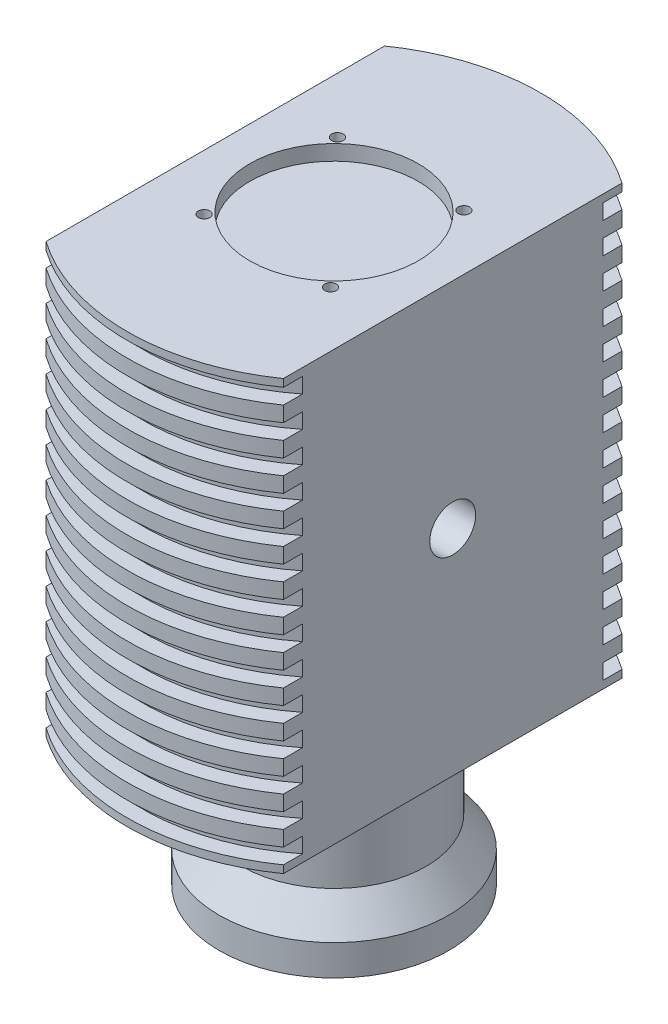
SolidWorks part; units mm, degrees
ref_plane "Front Plane" through (0, 0, 0) normal (0, 0, 1) x (1, 0, 0)
ref_plane "Top Plane" through (0, 0, 0) normal (0, 1, 0) x (1, 0, 0)
ref_plane "Right Plane" through (0, 0, 0) normal (1, 0, 0) x (0, 0, -1)
sketch "Sketch1" plane through (0, 0, 0) normal (0, 0, 1) x (1, 0, 0)
  line L0 (0, 0) -> (30, 0)
  line L1 (30, 0) -> (30, 8)
  line L2 (30, 8) -> (24, 16)
  line L3 (24, 16) -> (24, 40)
  line L9 (0, 76.2123) -> (0, -32.816) construction
  line L17 (24, 40) -> (54, 40)
  line L18 (54, 40) -> (54, 42)
  line L19 (54, 42) -> (50, 42)
  line L20 (50, 42) -> (50, 46)
  line L21 (50, 46) -> (54, 46)
  line L22 (54, 46) -> (54, 50)
  line L23 (54, 50) -> (50, 50)
  line L26 (0, 50) -> (0, 0)
  line L27 (50, 50) -> (50, 54)
  line L28 (50, 54) -> (54, 54)
  line L29 (54, 54) -> (54, 58)
  line L30 (54, 58) -> (50, 58)
  line L31 (50, 58) -> (50, 62)
  line L32 (50, 62) -> (54, 62)
  line L33 (54, 62) -> (54, 66)
  line L34 (54, 66) -> (50, 66)
  line L35 (50, 66) -> (50, 70)
  line L36 (50, 70) -> (54, 70)
  line L37 (54, 70) -> (54, 74)
  line L38 (54, 74) -> (50, 74)
  line L39 (50, 74) -> (50, 78)
  line L40 (50, 78) -> (54, 78)
  line L41 (54, 78) -> (54, 82)
  line L42 (54, 82) -> (50, 82)
  line L43 (50, 82) -> (50, 86)
  line L44 (50, 86) -> (54, 86)
  line L45 (54, 86) -> (54, 90)
  line L46 (54, 90) -> (50, 90)
  line L47 (50, 90) -> (50, 94)
  line L48 (50, 94) -> (54, 94)
  line L49 (54, 94) -> (54, 98)
  line L50 (54, 98) -> (50, 98)
  line L51 (50, 98) -> (50, 102)
  line L52 (50, 102) -> (54, 102)
  line L53 (54, 102) -> (54, 106)
  line L54 (54, 106) -> (50, 106)
  line L55 (50, 106) -> (50, 110)
  line L56 (50, 110) -> (54, 110)
  line L57 (54, 110) -> (54, 114)
  line L58 (54, 114) -> (50, 114)
  line L59 (50, 114) -> (50, 118)
  line L60 (50, 118) -> (54, 118)
  line L61 (54, 118) -> (54, 122)
  line L62 (54, 122) -> (50, 122)
  line L63 (50, 122) -> (50, 126)
  line L64 (50, 126) -> (54, 126)
  line L65 (54, 126) -> (54, 130)
  line L66 (54, 130) -> (50, 130)
  line L67 (50, 130) -> (50, 134)
  line L68 (50, 134) -> (54, 134)
  line L69 (54, 134) -> (54, 138)
  line L70 (54, 138) -> (50, 138)
  line L71 (50, 138) -> (50, 142)
  line L72 (50, 142) -> (54, 142)
  line L73 (54, 142) -> (54, 146)
  line L74 (54, 146) -> (50, 146)
  line L75 (50, 146) -> (50, 150)
  line L76 (50, 150) -> (54, 150)
  line L77 (54, 150) -> (54, 152)
  line L78 (54, 152) -> (0, 152)
  line L79 (0, 152) -> (0, 50)
  dimension "D1" = 8
  dimension "D2" = 8
  dimension "D3" = 24
  dimension "D4" = 50
  dimension "D5" = 4
  dimension "D6" = 30
  dimension "D7" = 2
  dimension "D8" = 4
  dimension "D9" = 4
  dimension "D10" = 4
  dimension "D11" = 4
  dimension "D12" = 4
  dimension "D13" = 4
  dimension "D14" = 4
  dimension "D15" = 4
  dimension "D16" = 4
  dimension "D17" = 4
  dimension "D18" = 4
  dimension "D19" = 4
  dimension "D20" = 4
  dimension "D21" = 4
  dimension "D22" = 4
  dimension "D23" = 4
  dimension "D24" = 4
  dimension "D25" = 4
  dimension "D26" = 4
  dimension "D27" = 4
  dimension "D28" = 4
  dimension "D29" = 4
  dimension "D30" = 4
  dimension "D31" = 4
  dimension "D32" = 4
  dimension "D33" = 4
  dimension "D34" = 4
  dimension "D35" = 4
  dimension "D36" = 4
  dimension "D37" = 4
  dimension "D38" = 2
revolve "Revolve1" add sketch "Sketch1" angle 360 about L9
sketch "Sketch4" plane through (0, 0, 0) normal (0, -1, 0) x (1, 0, 0)
  circle A0 centre (0, 0) radius 5
  circle A1 centre (0, 0) radius 30 construction
  dimension "D1" = 10
extrude "Cut-Extrude1" cut sketch "Sketch4" against normal blind 20
thread "Thread1" pitch 1.25 method cut profile "Thread Profile3" start angle 0, offset 0, length 0, pitch 1.25, diameter 10
ref_plane "Plane3" through (5, 0, 0) normal (0, 0, 1) x (1, 0, 0)
sketch "Thread Profile3" plane through (5, 0, 0) normal (0, 0, 1) x (1, 0, 0)
  line L0 (0, 0) -> (0, 1.25) construction
  line L1 (0, 0) -> (0.6766, 0.3906)
  line L2 (0.6766, 0.3906) -> (0.6766, 0.5469)
  line L3 (0.6766, 0.5469) -> (0, 0.9375)
  line L4 (0.6766, 0.4687) -> (0, 0.4687) construction
  line L11 (0, 0) -> (0, 0.9375)
  point P2 (0, 0)
  dimension "Pitch" = 1.25
  dimension "Profile_Angle" = 60
  dimension "Profile_Land" = 0.1562
  dimension "Profile_Height" = 0.6766
ref_plane "Plane4" through (0, 50, 0) normal (0, 1, 0) x (1, 0, 0)
sketch "Sketch7" plane through (0, 152, 0) normal (0, 1, 0) x (1, 0, 0)
  line L0 (-31, 44.2154) -> (-31, -44.2154)
  line L1 (31, 44.2154) -> (31, -44.2154)
  circle A0 centre (0, 0) radius 31
  circle A1 centre (0, 0) radius 54 construction
  arc A2 (-31, 44.2154) -> (-31, -44.2154) centre (0, 0) ccw
  arc A3 (31, -44.2154) -> (31, 44.2154) centre (0, 0) ccw
  circle M3 centre (0, 0) radius 54
  dimension "D1" = 62
extrude "Cut-Extrude2" cut sketch "Sketch7" against normal through all contours L0 M3 | L1 M3 region at (-40.3918, 152, 0) region at (40.3918, 152, 0)
sketch "Sketch8" plane through (-31, 0, 0) normal (-1, 0, 0) x (0, 0, 1)
  circle A0 centre (0, 96) radius 6
  dimension "D1" = 12
  dimension "D2" = 96
extrude "Cut-Extrude3" cut sketch "Sketch8" against normal through all
sketch "Sketch9" plane through (0, 152, 0) normal (0, 1, 0) x (1, 0, 0)
  circle A0 centre (0, 0) radius 22
  dimension "D1" = 44
extrude "Cut-Extrude4" cut sketch "Sketch9" against normal blind 4
sketch "Sketch10" plane through (0, 152, 0) normal (0, 1, 0) x (1, 0, 0)
  line L1 (24, 25.3043) -> (-24, 25.3043)
  line L2 (24, 25.3043) -> (24, -25.3043)
  line L3 (24, -25.3043) -> (-24, -25.3043)
  line L4 (-24, 25.3043) -> (-24, -25.3043)
  line L5 (24, 25.3043) -> (-24, -25.3043) construction
  line L6 (24, -25.3043) -> (-24, 25.3043) construction
  circle A0 centre (0, 0) radius 24
  circle A1 centre (-16.5158, 17.4134) radius 1.5
  circle A2 centre (16.5158, 17.4134) radius 1.5
  circle A3 centre (16.5158, -17.4134) radius 1.5
  circle A4 centre (-16.5158, -17.4134) radius 1.5
  dimension "D1" = 48
  dimension "D2" = 3
extrude "Cut-Extrude5" cut sketch "Sketch10" against normal blind 5 contours A0 A4 | A0 A2 | A0 A2 | A0 A1 | A0 A1 | A0 A3 | A0 A3 | A4 region at (16.072, 152, -16.9454) region at (16.9481, 152, -17.8691) region at (16.9481, 152, 17.8691) region at (16.072, 152, 16.9454) region at (-16.9481, 152, -17.8691) region at (-16.072, 152, -16.9454) region at (-16.9481, 152, 17.8691)
sketch "Sketch11" plane through (-31, 0, 0) normal (-1, 0, 0) x (0, 0, 1)
  circle A0 centre (0, 96) radius 28
  dimension "D1" = 56
extrude "Cut-Extrude6" cut sketch "Sketch11" against normal blind 4
sketch "Sketch12" plane through (-31, 0, 0) normal (-1, 0, 0) x (0, 0, 1)
  circle A1 centre (0, 133.5) radius 1.5
  circle A2 centre (32.476, 114.75) radius 1.5
  circle A3 centre (32.476, 77.25) radius 1.5
  circle A4 centre (0, 58.5) radius 1.5
  circle A5 centre (-32.476, 77.25) radius 1.5
  circle A6 centre (-32.476, 114.75) radius 1.5
  point P16 (0, 96)
  dimension "D1" = 6
  dimension "D2" = 3
extrude "Cut-Extrude7" cut sketch "Sketch12" against normal blind 4
